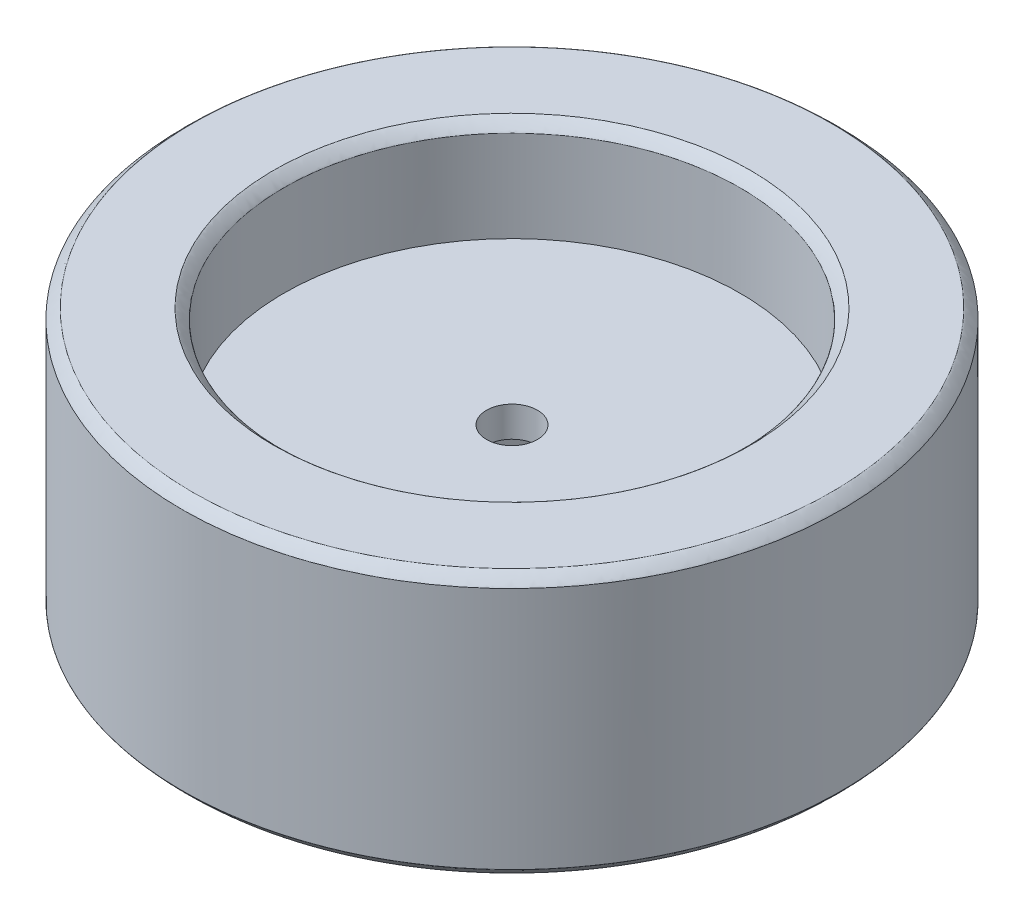
SolidWorks part; units mm, degrees
ref_plane "Front Plane" through (0, 0, 0) normal (0, 0, 1) x (1, 0, 0)
ref_plane "Top Plane" through (0, 0, 0) normal (0, 1, 0) x (1, 0, 0)
ref_plane "Right Plane" through (0, 0, 0) normal (1, 0, 0) x (0, 0, -1)
other "Configuration Table"
sketch "Sketch1" plane through (0, 0, 0) normal (0, 1, 0) x (1, 0, 0)
  line L1 (6.9282, 0) -> (3.4641, 6)
  line L2 (3.4641, 6) -> (-3.4641, 6)
  line L3 (-3.4641, 6) -> (-6.9282, 0)
  line L4 (-6.9282, 0) -> (-3.4641, -6)
  line L5 (-3.4641, -6) -> (3.4641, -6)
  line L6 (3.4641, -6) -> (6.9282, 0)
  circle A1 centre (0, 0) radius 32.5
  circle A3 centre (0, 0) radius 6 construction
  circle A4 centre (0, 0) radius 8
  circle A5 centre (0, 0) radius 2.51
  circle A6 centre (0, 0) radius 22.5
  dimension "D1" = 12
extrude "Boss-Extrude2" add sketch "Sketch1" along normal blind 26 contours A1
extrude "Cut-Extrude3" cut sketch "Sketch1<4>" along normal blind 13 contours A6
sketch "Sketch1<4>" plane through (0, 0, 0) normal (0, 1, 0) x (1, 0, 0) same geometry as "Sketch1"
extrude "Boss-Extrude3" add sketch "Sketch1<5>" along normal blind 13 contours A4
sketch "Sketch1<5>" plane through (0, 0, 0) normal (0, 1, 0) x (1, 0, 0) same geometry as "Sketch1"
extrude "Cut-Extrude4" cut sketch "Sketch1<6>" along normal blind 9 contours A4
sketch "Sketch1<6>" plane through (0, 0, 0) normal (0, 1, 0) x (1, 0, 0) same geometry as "Sketch1"
extrude "Cut-Extrude5" cut sketch "Sketch1<7>" along normal blind 13 contours L5 L6 L1 L2 L3 L4
sketch "Sketch1<7>" plane through (0, 0, 0) normal (0, 1, 0) x (1, 0, 0) same geometry as "Sketch1"
extrude "Cut-Extrude6" cut sketch "Sketch1<8>" along normal blind 31 contours A5
sketch "Sketch1<8>" plane through (0, 0, 0) normal (0, 1, 0) x (1, 0, 0) same geometry as "Sketch1"
sketch "Sketch2" plane through (0, 26, 0) normal (0, 1, 0) x (1, 0, 0)
  circle A0 centre (0, 0) radius 22.5
extrude "Cut-Extrude7" cut sketch "Sketch2" against normal blind 10 contours A0
fillet "Fillet1" radius 1 4 edges at (0, 26, 22.5) (0, 26, 32.5) (0, 0, 22.5) (0, 0, 32.5) conic radius 10
